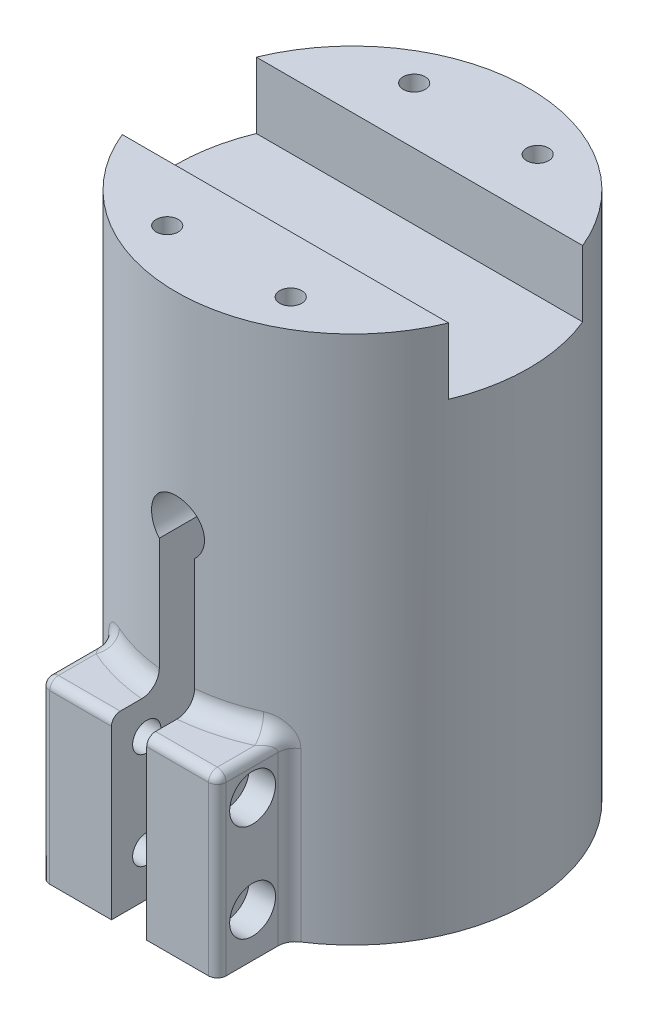
SolidWorks part; units mm, degrees
ref_plane "Front Plane" through (0, 0, 0) normal (0, 0, 1) x (1, 0, 0)
ref_plane "Top Plane" through (0, 0, 0) normal (0, 1, 0) x (1, 0, 0)
ref_plane "Right Plane" through (0, 0, 0) normal (1, 0, 0) x (0, 0, -1)
sketch "Sketch1" plane through (0, 0, 0) normal (0, 1, 0) x (1, 0, 0)
  circle A0 centre (0, 0) radius 20
  dimension "D1" = 40
extrude "Boss-Extrude1" add sketch "Sketch1" along normal blind 60
sketch "Sketch3" plane through (0, 0, 0) normal (0, -1, 0) x (1, 0, 0)
  circle A0 centre (0, 0) radius 12.6
  dimension "D1" = 25.2
extrude "Cut-Extrude1" cut sketch "Sketch3" against normal blind 40
sketch "Sketch5" plane through (0, 0, 0) normal (0, -1, 0) x (-1, 0, 0)
  line L1 (10, -25.3205) -> (-10, -25.3205)
  line L2 (10, -25.3205) -> (10, -17.3205)
  line L4 (-10, -25.3205) -> (-10, -17.3205)
  arc A2 (-10, -17.3205) -> (10, -17.3205) centre (0, 0) ccw
  dimension "D5" = 20
  dimension "D1" = 20
  dimension "D2" = 10
  dimension "D4" = 8
extrude "Boss-Extrude3" add sketch "Sketch5" against normal blind 20
sketch "Sketch6" plane through (0, 0, 0) normal (1, 0, 0) x (0, 0, -1)
  line L4 (7.6, 60) -> (7.6, 52.5)
  line L5 (20, 60) -> (-20, 60) construction
  line L7 (7.6, 52.5) -> (-7.6, 52.5)
  line L8 (-7.6, 52.5) -> (-7.6, 60)
  line L9 (-7.6, 60) -> (7.6, 60)
  point P1 (0, 60)
  dimension "D1" = 15.2
  dimension "D2" = 7.6
  dimension "D3" = 0
  dimension "D4" = 7.5
extrude "Cut-Extrude2" cut sketch "Sketch6" against normal blind 20 and the other way blind 20
sketch "Sketch7" plane through (0, 0, 0) normal (0, -1, 0) x (1, 0, 0)
  line L0 (10, 25.3205) -> (-10, 25.3205) construction
  line L1 (2, 10.3205) -> (-2, 10.3205)
  line L2 (2, 10.3205) -> (2, 25.3205)
  line L3 (2, 25.3205) -> (-2, 25.3205)
  line L4 (-2, 10.3205) -> (-2, 25.3205)
  dimension "D1" = 4
  dimension "D2" = 2
  dimension "D3" = 15
extrude "Cut-Extrude3" cut sketch "Sketch7" against normal blind 38
sketch "Sketch8" plane through (0, 0, 0) normal (0, 0, 1) x (1, 0, 0)
  circle A0 centre (0, 37) radius 3
  dimension "D1" = 6
  dimension "D2" = 37
extrude "Cut-Extrude4" cut sketch "Sketch8" along normal blind 20 contours A0
fillet "Fillet1" radius 1 6 edges at (-6, 20, 25.3205) (-10, 20, 21.3205) (10, 20, 21.3205) (6, 20, 25.3205) (-10, 10, 25.3205) (10, 10, 25.3205)
fillet "Fillet2" radius 2 6 edges at (5.5937, 20, 19.2018) (9.6887, 19.725, 17.4965) (-5.5937, 20, 19.2018) (-9.8257, 19.5641, 17.42) (10, 9.5, 17.3205) (-10, 9.5, 17.3205)
sketch "Sketch9" plane through (10, 0, 0) normal (1, 0, 0) x (0, 0, -1)
  line L0 (-25.3205, 0) -> (-25.3205, 19) construction
  line L1 (-18.4391, 0) -> (-24.3205, 0) construction
  line L2 (-24.3205, 20) -> (-20.0749, 20) construction
  circle A0 centre (-21.3205, 5) radius 1.6
  circle A1 centre (-21.3205, 16) radius 1.6
  dimension "D1" = 3.2
  dimension "D4" = 3.2
  dimension "D2" = 4
  dimension "D3" = 5
  dimension "D5" = 4
  dimension "D6" = 4
extrude "Cut-Extrude5" cut sketch "Sketch9" against normal blind 20
sketch "Sketch10" plane through (10, 0, 0) normal (1, 0, 0) x (0, 0, -1)
  circle A0 centre (-21.3205, 5) radius 2.6
  circle A1 centre (-21.3205, 16) radius 2.6
  dimension "D1" = 5.2
  dimension "D2" = 5.2
extrude "Cut-Extrude6" cut sketch "Sketch10" against normal blind 3
sketch "Sketch11" plane through (-10, 0, 0) normal (-1, 0, 0) x (0, 0, 1)
  line L1 (24.3227, 16) -> (22.8216, 18.6)
  line L2 (22.8216, 18.6) -> (19.8194, 18.6)
  line L3 (19.8194, 18.6) -> (18.3183, 16)
  line L4 (18.3183, 16) -> (19.8194, 13.4)
  line L5 (19.8194, 13.4) -> (22.8216, 13.4)
  line L6 (22.8216, 13.4) -> (24.3227, 16)
  line L7 (24.3227, 5) -> (22.8216, 7.6)
  line L8 (22.8216, 7.6) -> (19.8194, 7.6)
  line L9 (19.8194, 7.6) -> (18.3183, 5)
  line L10 (18.3183, 5) -> (19.8194, 2.4)
  line L11 (19.8194, 2.4) -> (22.8216, 2.4)
  line L12 (22.8216, 2.4) -> (24.3227, 5)
  circle A0 centre (21.3205, 16) radius 2.6 construction
  circle A1 centre (21.3205, 5) radius 2.6 construction
  dimension "D1" = 5.2
  dimension "D2" = 5.2
extrude "Cut-Extrude7" cut sketch "Sketch11" against normal blind 3
sketch "Sketch12" plane through (0, 60, 0) normal (0, 1, 0) x (1, 0, 0)
  circle A0 centre (-7, 14) radius 1.25
  circle A1 centre (-7, -14) radius 1.25
  circle A2 centre (7, 14) radius 1.25
  circle A3 centre (7, -14) radius 1.25
  dimension "D3" = 2.5
  dimension "D4" = 2.5
  dimension "D7" = 2.5
  dimension "D8" = 2.5
  dimension "D1" = 14
  dimension "D2" = 14
  dimension "D5" = 7
  dimension "D6" = 7
  dimension "D9" = 7
  dimension "D10" = 7
  dimension "D11" = 14
  dimension "D12" = 14
extrude "Cut-Extrude10" cut sketch "Sketch12" against normal blind 15
